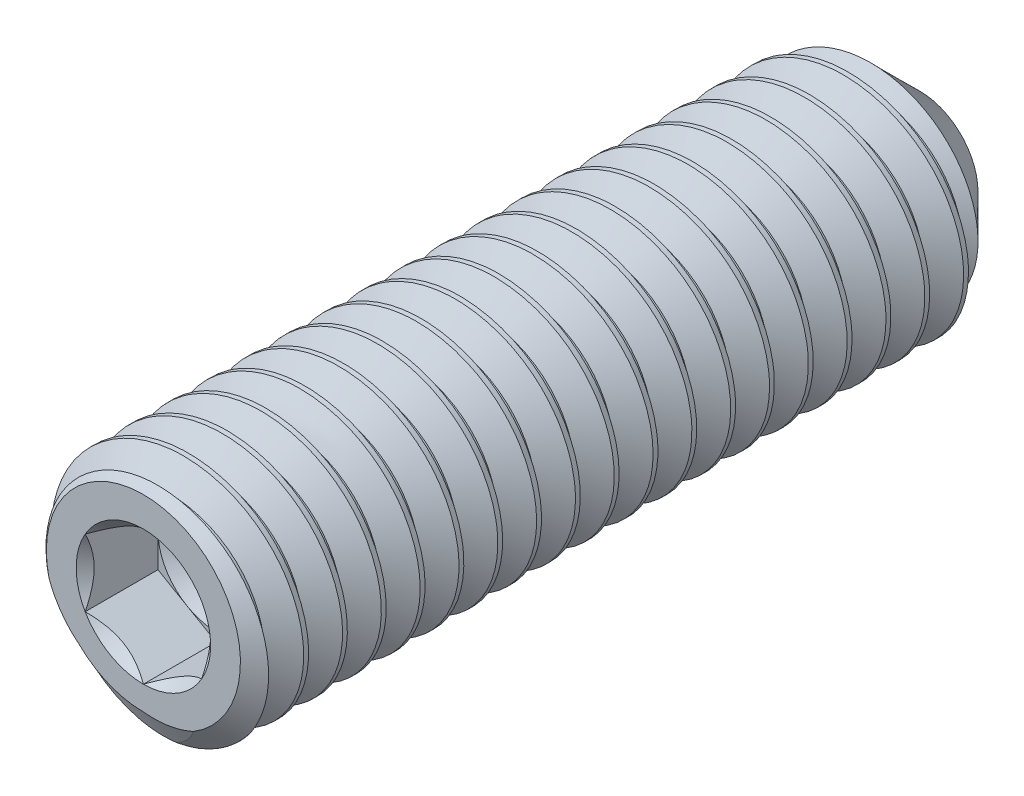
SolidWorks part; units mm, degrees
other "Imported1" parameters "D3"=11, "D1"=46.842, "Length"=10, "Drive Size"=1.5, "Thread Size"=3, "Thread Pitch"=0.5, "hex Depth"=0.9375, "D2"=0.9112, "Dia"=12, "D4"=2.3829, "Cup Point Dia"=3.3528, "D5"=1.436, "D6"=1.4986, "D7"=5.0014, "Pitch"=1.75
ref_plane "Front" through (0, 0, 0) normal (0, 0, 1) x (1, 0, 0)
ref_plane "Top" through (0, 0, 0) normal (0, 1, 0) x (1, 0, 0)
ref_plane "Right" through (0, 0, 0) normal (1, 0, 0) x (0, 0, -1)
sketch "Sketch1" plane through (0, 0, 0) normal (1, 0, 0) x (0, 0, -1)
  line L0 (5, 1.5) -> (-5, 1.5) construction
  line L1 (-5, 1.5) -> (-5, -1.5) construction
  line L2 (-5, -1.5) -> (5, -1.5) construction
  line L3 (5, -1.5) -> (5, 1.5) construction
  line L4 (-5, 0.75) -> (-5, -0.75) construction
  line L5 (4.9688, 1.5541) -> (5.4688, 1.5541) construction
  line L6 (5.4688, 1.5541) -> (5.2188, 1.1211) construction
  line L7 (5.2188, 1.1211) -> (4.9688, 1.5541) construction
  line L8 (4.9844, 1.5271) -> (5.4531, 1.5271) construction
  line L9 (5, 1.5) -> (5.4375, 1.5) construction
  line L10 (5.2188, 1.5541) -> (5.2188, 1.5) construction
  line L11 (5.1875, 1.1752) -> (5.25, 1.1752) construction
  line L12 (5.2188, 1.1752) -> (5.2188, 1.1211) construction
  point P3 (0, 1.5)
  point P19 (5.2188, 1.5271)
  point P24 (-5, 0)
  point P25 (-5, 0)
  dimension "D1" = 0.0625
sketch "Sketch11" plane through (0, 0, 0) normal (1, 0, 0) x (0, 0, -1)
  line L0 (-5, 0) -> (-5, 1.25)
  line L1 (-5, 1.25) -> (-4.8249, 1.5)
  line L2 (-4.8249, 1.5) -> (4.25, 1.5)
  line L3 (4.25, 1.5) -> (5, 0.75)
  line L4 (5, 0.75) -> (4.5494, 0)
  line L5 (4.5494, 0) -> (-5, 0)
  line L6 (4.5494, 0) -> (5, 0) construction
  line L7 (5, 0) -> (5, 0.75) construction
  line L8 (5, -0.75) -> (4.5494, 0) construction
  line L9 (-4.8249, -1.5) -> (4.25, -1.5) construction
  line L10 (-5, -1.5) -> (5, -1.5) construction
  line L11 (-5, 1.5) -> (-5, -1.5) construction
  line L12 (5, -1.5) -> (5, 1.5) construction
  point P11 (3.25, -1.5)
  point P12 (-5, 1.5)
  dimension "D3" = 35
  dimension "D5" = 118
  dimension "D6" = 45
  dimension "D1" = 0.25
  dimension "D2" = 1.75
  dimension "D4" = 0.75
revolve "Revolve1" add sketch "Sketch11" angle 360 about L6
sketch "Sketch2" plane through (0, 0, 5) normal (0, 0, 1) x (1, 0, 0)
  line L1 (0, 0.866) -> (-0.75, 0.433)
  line L2 (-0.75, 0.433) -> (-0.75, -0.433)
  line L3 (-0.75, -0.433) -> (0, -0.866)
  line L4 (0, -0.866) -> (0.75, -0.433)
  line L5 (0.75, -0.433) -> (0.75, 0.433)
  line L6 (0.75, 0.433) -> (0, 0.866)
  circle A0 centre (0, 0) radius 0.75 construction
  circle A1 centre (0, 0) radius 1.5 construction
extrude "Cut-Extrude1" cut sketch "Sketch2" against normal blind 0.9375
sketch "Sketch3" plane through (0, 0, 5) normal (0, 0, 1) x (1, 0, 0)
  circle A0 centre (0, 0) radius 0.866
extrude "Cut-Extrude2" cut sketch "Sketch3" against normal through all draft 45
sketch "Sketch4" plane through (0, 0, 4.0625) normal (0, 0, 1) x (1, 0, 0)
  circle A0 centre (0, 0) radius 0.75 construction
  circle A1 centre (0, 0) radius 0.75
extrude "Cut-Extrude3" cut sketch "Sketch4" against normal through all draft 60
sketch "Sketch13" plane through (0, 0, 0) normal (1, 0, 0) x (0, 0, -1)
  line L0 (0, -1.5) -> (0, 1.5) construction
  line L2 (-4.8249, 1.5) -> (4.25, 1.5) construction
  line L4 (4.5494, 0) -> (-5, 0) construction
  point P0 (1.5494, 0)
  point P4 (0, 0)
  point P9 (-1.5494, 0)
  dimension "D1" = 3
ref_plane "Plane1" through (0, 0, -5) normal (0, 0, 1) x (1, 0, 0)
sketch "Sketch5" plane through (0, 0, -5) normal (0, 0, 1) x (1, 0, 0)
  circle A0 centre (0, 0) radius 1.5 construction
  circle A1 centre (0, 0) radius 1.5
curve "Helix/Spiral1" pitch 0.5 height 11 radius 1.5 centre (0, 0, -5) axis (0, 0, 1) start towards (0, 1, 0)
sketch "Sketch6" plane through (0, 0, 0) normal (1, 0, 0) x (0, 0, -1)
  line L0 (4.9687, 1.5541) -> (5.4688, 1.5541) construction
  line L1 (5.4688, 1.5541) -> (5.2187, 1.1211) construction
  line L2 (5.2187, 1.1211) -> (4.9687, 1.5541) construction
  line L3 (5.2187, 1.5541) -> (5.2187, 1.5) construction
  line L4 (5, 1.5) -> (5.4375, 1.5) construction
  line L5 (5.2187, 1.1752) -> (5.2187, 1.1211) construction
  line L6 (5.1875, 1.1752) -> (4.9844, 1.5271)
  line L7 (4.9844, 1.5271) -> (5.4531, 1.5271)
  line L8 (4.9844, 1.5271) -> (5.4531, 1.5271) construction
  line L10 (5.1875, 1.1752) -> (5.25, 1.1752) construction
  line L12 (5.25, 1.1752) -> (5.1875, 1.1752)
  line L13 (5.4531, 1.5271) -> (5.25, 1.1752)
  point P9 (5.2187, 1.5)
  point P14 (5.2187, 1.5271)
  point P15 (5.2187, 1.5271)
  point P16 (5.2187, 1.1752)
  dimension "D1" = 0.5
  dimension "D2" = 0.0625
sweep "Cut-Sweep1" cut profiles "Sketch6" path "Helix/Spiral1"
equation "\"D3@Helix/Spiral1\" = \"Length@Sketch1\" * 1.1"
equation "\"hex Depth@Cut-Extrude1\" = \"Drive Size@Sketch1\" * .625"
equation "\"D1@Sketch6\" = \"Thread Pitch@Sketch1\""
equation "\"D2@Sketch6\" = \"D1@Sketch6\" / 8"
equation "\"D1@Sketch11\" = \"Thread Pitch@Sketch1\" * .5"
equation "\"D2@Sketch11\" = \"Thread Pitch@Sketch1\" * 3.5"
equation "\"D1@Helix/Spiral1\" = \"Thread Pitch@Sketch1\""
equation "\"D4@Sketch11\" = \"Thread Pitch@Sketch1\" * 1.5"
equation "\"D1@Sketch1\" = \"Thread Pitch@Sketch1\" / 8"
equation "\"D1@Sketch13\"=\"Thread Size@Sketch1\""
